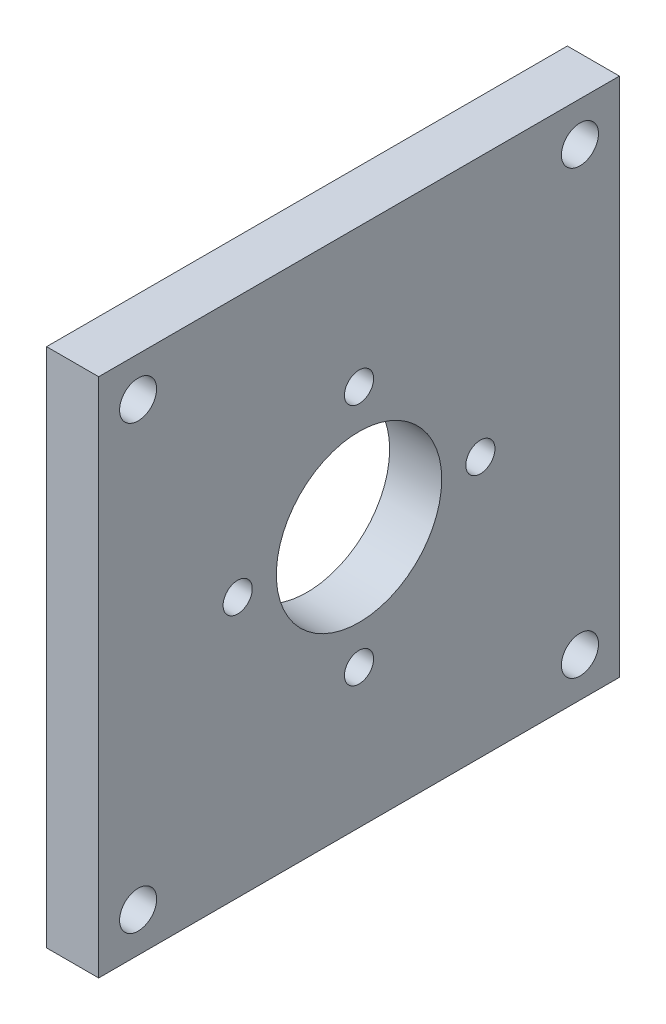
SolidWorks part; units mm, degrees
material "2024 Alloy"
ref_plane "Front Plane" through (0, 0, 0) normal (0, 0, 1) x (1, 0, 0)
ref_plane "Top Plane" through (0, 0, 0) normal (0, 1, 0) x (1, 0, 0)
ref_plane "Right Plane" through (0, 0, 0) normal (1, 0, 0) x (0, 0, -1)
sketch "Sketch1" plane through (0, 0, 0) normal (1, 0, 0) x (0, 0, -1)
  line L1 (-15.875, -15.875) -> (15.875, -15.875)
  line L2 (-15.875, -15.875) -> (-15.875, 15.875)
  line L3 (-15.875, 15.875) -> (15.875, 15.875)
  line L4 (15.875, -15.875) -> (15.875, 15.875)
  line L5 (-15.875, -15.875) -> (15.875, 15.875) construction
  line L6 (-15.875, 15.875) -> (15.875, -15.875) construction
  point P0 (0, 0)
  dimension "D1" = 31.75
  dimension "D2" = 31.75
extrude "Boss-Extrude1" add sketch "Sketch1" along normal blind 3.175
hole_wizard "X (0.397) Diameter Hole1" positions "Sketch3" profile "Sketch2" hole size "X" standard "ANSI Inch"
sketch "Sketch3" plane through (3.175, 0, 0) normal (1, 0, 0) x (0, 0, -1)
  point P0 (0, 0)
sketch "Sketch2" plane through (3.175, 0, 0) normal (0, 1, 0) x (0, 0, -1)
  line L0 (0, 0) -> (0, 15.7295)
  line L1 (0, 15.7295) -> (5.0419, 12.7)
  line L2 (5.0419, 12.7) -> (5.0419, 0)
  line L5 (5.0419, 0) -> (0, 0)
  line L10 (0, 15.7295) -> (-5.0419, 12.7) construction
  line L11 (0, -6.35) -> (0, 107.95) construction
  dimension "Hole Dia." = 10.0838
  dimension "Hole Depth" = 12.7
  dimension "Drill Angle" = 118
hole_wizard "#2-56 Tapped Hole1" positions "Sketch5" profile "Sketch4" tap size "#2-56" standard "ANSI Inch"
sketch "Sketch5" plane through (3.175, 0, 0) normal (1, 0, 0) x (0, 0, -1)
  point P0 (0, 7.4)
  dimension "D1" = 7.4
sketch "Sketch4" plane through (3.175, 7.4, 0) normal (0, 1, 0) x (0, 0, -1)
  line L0 (0, 0) -> (0, 7.1382)
  line L1 (0, 7.1382) -> (0.889, 6.604)
  line L2 (0.889, 6.604) -> (0.889, 0)
  line L5 (0.889, 0) -> (0, 0)
  line L10 (0, 7.1382) -> (-0.889, 6.604) construction
  line L11 (0, -6.35) -> (0, 107.95) construction
  dimension "Tap Drill Dia." = 1.778
  dimension "Tap Drill Depth" = 6.604
  dimension "Drill Angle" = 118
pattern_circular "CirPattern1" count 4 over 360 about axis through (3.175, 0, 0) along (1, 0, 0) of "#2-56 Tapped Hole1"
hole_wizard "#4-40 Tapped Hole1" positions "Sketch7" profile "Sketch6" tap size "#4-40" standard "ANSI Inch"
sketch "Sketch7" plane through (3.175, 0, 0) normal (1, 0, 0) x (0, 0, -1)
  line L0 (0, -15.875) -> (0, 15.875) construction
  line L1 (-15.875, -15.875) -> (15.875, -15.875) construction
  line L2 (15.875, 15.875) -> (-15.875, 15.875) construction
  line L3 (0, 0) -> (-13.4704, 13.4704) construction
  point P0 (-13.4704, 13.4704)
  dimension "D1" = 45
  dimension "D2" = 19.05
sketch "Sketch6" plane through (3.175, 13.4704, 13.4704) normal (0, 1, 0) x (0, 0, -1)
  line L0 (0, 0) -> (0, 9.5692)
  line L1 (0, 9.5692) -> (1.1303, 8.89)
  line L2 (1.1303, 8.89) -> (1.1303, 0)
  line L5 (1.1303, 0) -> (0, 0)
  line L10 (0, 9.5692) -> (-1.1303, 8.89) construction
  line L11 (0, -6.35) -> (0, 107.95) construction
  dimension "Tap Drill Dia." = 2.2606
  dimension "Tap Drill Depth" = 8.89
  dimension "Drill Angle" = 118
pattern_circular "CirPattern2" count 4 over 360 about axis through (3.175, 0, 0) along (1, 0, 0) of "#4-40 Tapped Hole1"
